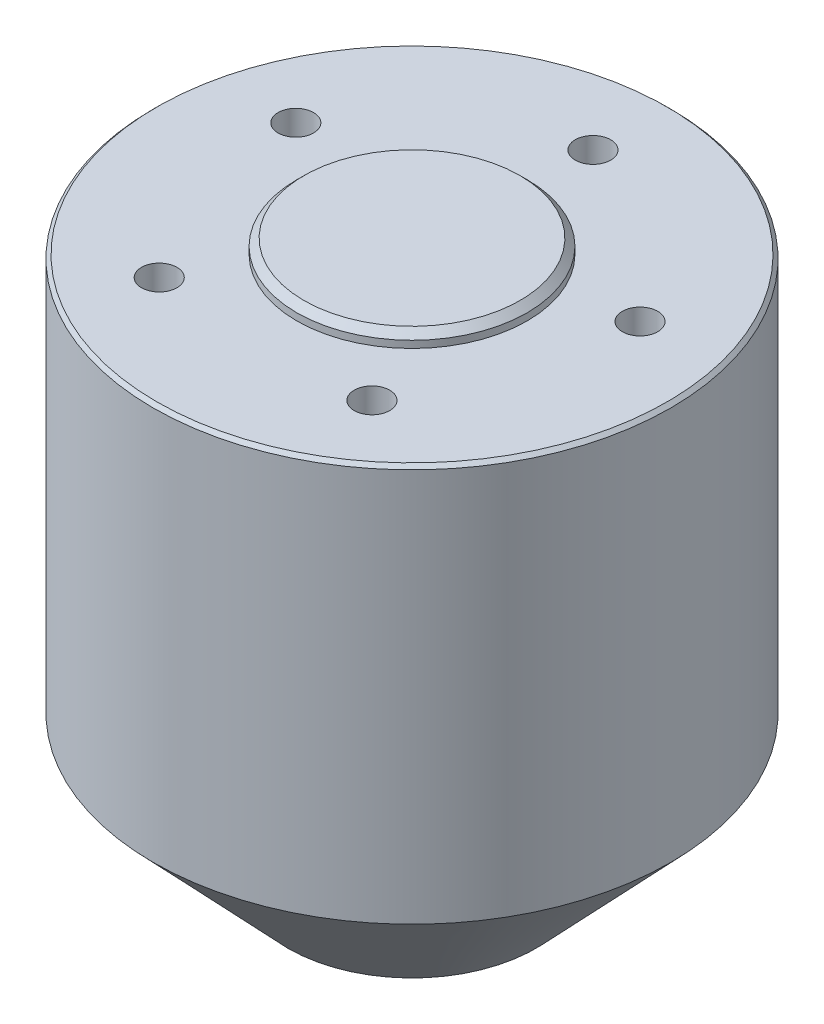
SolidWorks part; units mm, degrees
ref_plane "Front Plane" through (0, 0, 0) normal (0, 0, 1) x (1, 0, 0)
ref_plane "Top Plane" through (0, 0, 0) normal (0, 1, 0) x (1, 0, 0)
ref_plane "Right Plane" through (0, 0, 0) normal (1, 0, 0) x (0, 0, -1)
sketch "Sketch1" plane through (0, 0, 0) normal (0, 1, 0) x (1, 0, 0)
  circle A1 centre (0, 0) radius 36.5
  circle A2 centre (0, 0) radius 16.25
  dimension "D2" = 73
  dimension "D3" = 32.5
extrude "Boss-Extrude1" add sketch "Sketch1" along normal blind 76 contours A1 A2 region at (-35.4676, 0, 0)
extrude "Boss-Extrude2" add sketch "Sketch1<3>" along normal blind 78 contours A2 region at (0, 0, 0)
sketch "Sketch1<3>" plane through (0, 0, 0) normal (0, 1, 0) x (1, 0, 0) same geometry as "Sketch1"
sketch "Sketch2" plane through (0, 76, 0) normal (0, 1, 0) x (1, 0, 0)
  circle A0 centre (0, 0) radius 25.52 construction
  circle A1 centre (0, 25.52) radius 2.5
  circle A2 centre (24.271, 7.8861) radius 2.5
  circle A3 centre (15.0003, -20.6461) radius 2.5
  circle A4 centre (-15.0003, -20.6461) radius 2.5
  circle A5 centre (-24.271, 7.8861) radius 2.5
  point P5 (15.5655, -20.2234)
  point P6 (24.2924, 7.82)
  point P15 (0, 0)
  dimension "D1" = 51.04
  dimension "D3" = 5
  dimension "D2" = 5
extrude "Cut-Extrude1" cut sketch "Sketch2" against normal blind 7 contours A1 | A2 | A3 | A4 | A5
chamfer "Chamfer1" distance 0.5 1 edges at (0, 76, 36.5)
chamfer "Chamfer3" distance 1 1 edges at (0, 78, 16.25)
chamfer "Chamfer4" distance 19 distance2 20 1 edges at (0, 0, 36.5) first distance on face at (0, 0, 36.5)
